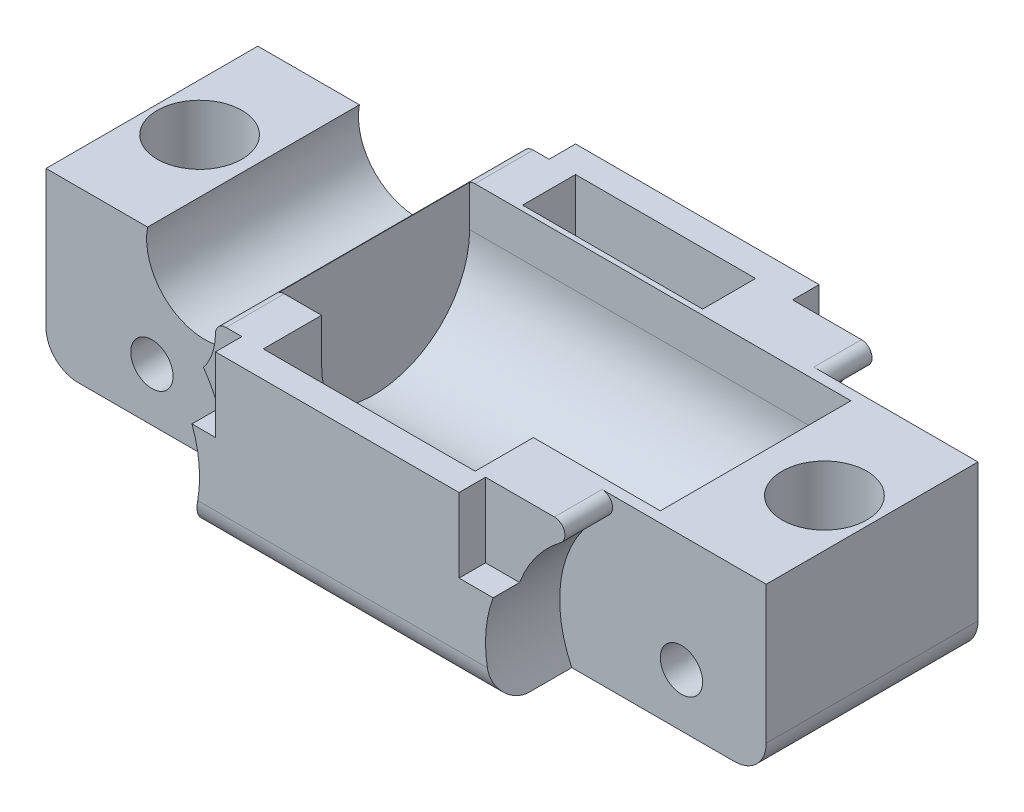
SolidWorks part; units mm, degrees
material "ABS"
ref_plane "Front Plane" through (0, 0, 0) normal (0, 0, 1) x (1, 0, 0)
ref_plane "Top Plane" through (0, 0, 0) normal (0, 1, 0) x (1, 0, 0)
ref_plane "Right Plane" through (0, 0, 0) normal (1, 0, 0) x (0, 0, -1)
sketch "Sketch1" plane through (0, 0, 0) normal (0, 1, 0) x (1, 0, 0)
  line L1 (-34, 17) -> (34, 17)
  line L2 (-34, 17) -> (-34, -17)
  line L3 (-34, -17) -> (34, -17)
  line L4 (34, 17) -> (34, -17)
  line L5 (-34, 17) -> (34, -17) construction
  line L6 (-34, -17) -> (34, 17) construction
  point P0 (0, 0)
  dimension "D1" = 68
  dimension "D2" = 34
extrude "Boss-Extrude1" add sketch "Sketch1" along normal blind 16
sketch "Sketch2" plane through (0, 0, 0) normal (0, 0, 1) x (1, 0, 0)
  point P0 (-24, 5)
  point P1 (26, 5)
  dimension "D1" = 50
  dimension "D2" = 26
  dimension "D3" = 5
sketch "Sketch3" plane through (0, 0, 0) normal (0, 0, 1) x (1, 0, 0)
  line L0 (26, 16.5) -> (37.5, 16.5)
  line L1 (37.5, 16.5) -> (37.5, 5)
  line L2 (37.5, 5) -> (37.5, -6.5)
  line L3 (37.5, -6.5) -> (26, -6.5)
  line L4 (-24, -6.5) -> (-35.5, -6.5)
  line L5 (-35.5, -6.5) -> (-35.5, 16.5)
  line L6 (-35.5, 16.5) -> (-24, 16.5)
  circle A0 centre (-24, 5) radius 11.5
  circle A1 centre (26, 5) radius 11.5
  dimension "D1" = 23
extrude "Cut-Extrude2" cut sketch "Sketch3" along normal blind 10 from offset 10 contours A1 L3 L2 | A1 | A1 L1 L0 | A0 | A0 L5 L4 | A0 L6 L5 region at (34.9313, 13.9313, 0) region at (26, 5, 0) region at (34.9313, -3.9313, 0) region at (-24, 5, 0) region at (-32.9313, -3.9313, 0) region at (-32.9313, 13.9313, 0)
mirror "Mirror1" about plane through (0, 0, 0) normal (0, 0, 1) of "Cut-Extrude2"
sketch "Sketch5" plane through (0, 0, 0) normal (0, 0, 1) x (1, 0, 0)
  circle A0 centre (26, 5) radius 2
  circle A1 centre (-24, 5) radius 2
  dimension "D1" = 4
extrude "Cut-Extrude3" cut sketch "Sketch5" against normal through all both and the other way through all
sketch "Sketch4" plane through (0, 0, 0) normal (1, 0, 0) x (0, 0, -1)
  line L0 (-9, 12) -> (-9, 23.0528)
  line L1 (-9, 23.0528) -> (9, 23.0528)
  line L2 (9, 23.0528) -> (9, 12)
  circle A0 centre (0, 12) radius 9
  dimension "D1" = 18
  dimension "D2" = 12
extrude "Battery" add sketch "Sketch4" along normal blind 23 and the other way blind 13 separate body contours A0 | A0 L2 L1 L0 region at (0, 17.5264, 8.7888) region at (0, 12, 0)
combine bodies "Combine1" operation type subtract main body 106 bodies to subtract 104
sketch "Sketch13" plane through (0, 16, 0) normal (0, 1, 0) x (1, 0, 0)
  circle A0 centre (29.5, 0) radius 4
  circle A1 centre (-29.5, 0) radius 4
  dimension "D1" = 8
  dimension "D3" = 5.5
  dimension "D2" = 3.5
extrude "MountHole" cut sketch "Sketch13" against normal blind 6
sketch "Sketch6" plane through (0, 0, 0) normal (0, 1, 0) x (1, 0, 0)
  line L1 (8.5, 9.5) -> (-8.5, 9.5)
  line L2 (8.5, 9.5) -> (8.5, 14.5)
  line L3 (8.5, 14.5) -> (-8.5, 14.5)
  line L4 (-8.5, 9.5) -> (-8.5, 14.5)
  line L5 (8.5, 9.5) -> (-8.5, 14.5) construction
  line L6 (8.5, 14.5) -> (-8.5, 9.5) construction
  point P0 (0, 12)
  dimension "D1" = 17
  dimension "D2" = 5
  dimension "D3" = 12
extrude "Charger" cut sketch "Sketch6" along normal up to next from offset 3
sketch "Sketch7" plane through (0, 0, 0) normal (0, -1, 0) x (1, 0, 0)
  line L1 (6, -16) -> (-6, -16)
  line L2 (6, -16) -> (6, -8)
  line L3 (6, -8) -> (-6, -8)
  line L4 (-6, -16) -> (-6, -8)
  line L5 (6, -16) -> (-6, -8) construction
  line L6 (6, -8) -> (-6, -16) construction
  point P0 (0, -12)
  dimension "D1" = 12
  dimension "D2" = 8
extrude "MicroUSB" cut sketch "Sketch7" against normal blind 3
fillet "Fillet1" radius 1.5 2 edges at (0, 3, -16) (0, 3, -8)
sketch "Sketch8" plane through (0, 0, 0) normal (0, 0, 1) x (1, 0, 0)
  circle A0 centre (-19, 15) radius 5.5
  dimension "D1" = 11
  dimension "D2" = 19
  dimension "D3" = 15
extrude "Motor" cut sketch "Sketch8" against normal through all both and the other way through all
fillet "BottomFillet_3mm" radius 3 4 edges at (1, 0, 17) (1, 0, -17) (34, 0, 0) (-34, 0, 0)
fillet "Fillet_1mm" radius 1 3 edges at (22.6459, 16, 13.5) (22.6459, 16, -13.5) (-13.5917, 16, 0)
sketch "Sketch10" plane through (0, 16, 0) normal (0, 1, 0) x (1, 0, 0)
  line L0 (-12.5, -17) -> (18.5, -17) construction
  line L1 (-8.983, -8.5) -> (11.017, -8.5)
  line L2 (-8.983, -8.5) -> (-8.983, -14.5)
  line L3 (-8.983, -14.5) -> (11.017, -14.5)
  line L4 (11.017, -8.5) -> (11.017, -14.5)
  line L5 (-8.983, -8.5) -> (11.017, -14.5) construction
  line L6 (-8.983, -14.5) -> (11.017, -8.5) construction
  point P0 (1.017, -11.5)
  dimension "D1" = 20
  dimension "D2" = 6
  dimension "D3" = 2.5
extrude "ControlBoard" cut sketch "Sketch10" against normal blind 12
fillet "Fillet2" radius 2 1 edges at (1.017, 9.042, 8.5)
hole_wizard "CSK for M3 Flat Head Machine Screw1" positions "Sketch11" profile "Sketch12" countersink size "M3" standard "ANSI Metric"
sketch "Sketch11" plane through (0, 0, 0) normal (0, -1, 0) x (-1, 0, 0)
  point P0 (-29.5, 0)
  point P5 (29.5, 0)
sketch "Sketch12" plane through (29.5, 0, 0) normal (1, 0, 0) x (0, 0, -1)
  line L0 (0, 0) -> (0, 11.0815)
  line L1 (0, 11.0815) -> (1.8, 10)
  line L2 (1.8, 10) -> (1.8, 1.35)
  line L3 (1.8, 1.35) -> (3.15, 0)
  line L5 (3.15, 0) -> (0, 0)
  line L6 (-1.8, 1.35) -> (-3.15, 0) construction
  line L10 (0, 11.0815) -> (-1.8, 10) construction
  line L11 (0, -6.35) -> (0, 107.95) construction
  dimension "Hole Dia." = 3.6
  dimension "Hole Depth" = 10
  dimension "Near C'Sink Dia." = 6.3
  dimension "Near C'Sink Angle" = 90
  dimension "Drill Angle" = 118
sketch "Sketch14" plane through (0, 0, 0) normal (0, 0, 1) x (1, 0, 0)
  line L1 (25.8393, 9) -> (12, 9)
  line L2 (25.8393, 9) -> (25.8393, 23.5989)
  line L3 (25.8393, 23.5989) -> (12, 23.5989)
  line L4 (12, 9) -> (12, 23.5989)
  line L5 (-22.7748, 9) -> (-11, 9)
  line L6 (-22.7748, 9) -> (-22.7748, 22.7145)
  line L7 (-22.7748, 22.7145) -> (-11, 22.7145)
  line L8 (-11, 9) -> (-11, 22.7145)
  dimension "D1" = 12
  dimension "D2" = 11
  dimension "D3" = 9
extrude "Cut-Extrude5" cut sketch "Sketch14" along normal blind 2.5 from vertex starting at point (18.5, 16, -17)
extrude "Cut-Extrude6" cut sketch "Sketch14<2>" against normal blind 2.5 from vertex starting at point (18.5, 16, 17)
sketch "Sketch14<2>" plane through (0, 0, 0) normal (0, 0, 1) x (1, 0, 0) same geometry as "Sketch14"
